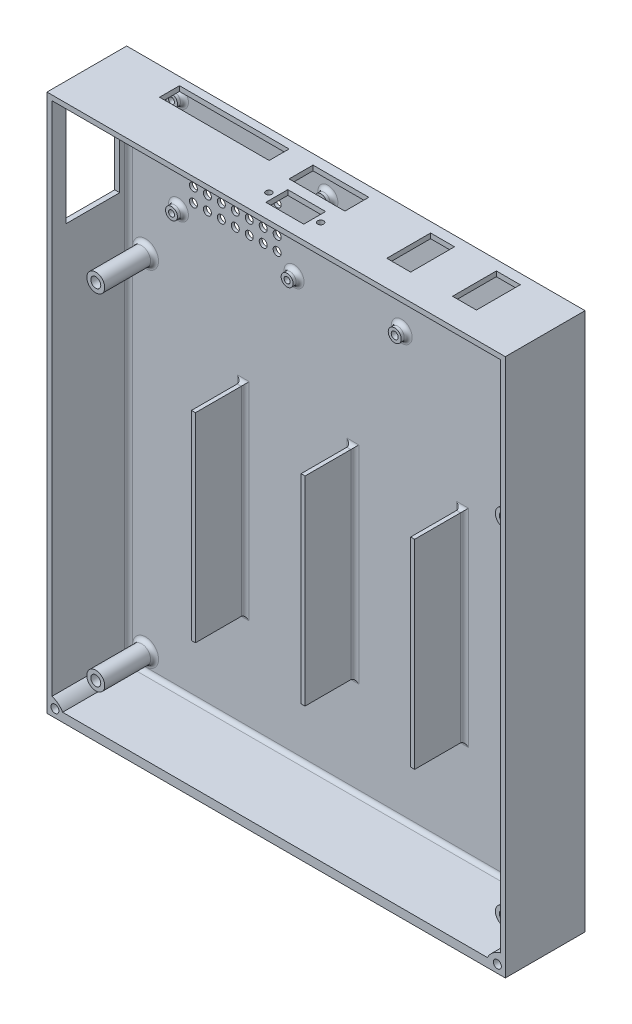
SolidWorks part; units mm, degrees
ref_plane "Plan de face" through (0, 0, 0) normal (0, 0, 1) x (1, 0, 0)
ref_plane "Plan de dessus" through (0, 0, 0) normal (0, 1, 0) x (1, 0, 0)
ref_plane "Plan de droite" through (0, 0, 0) normal (1, 0, 0) x (0, 0, -1)
sketch "Esquisse1" plane through (0, 0, 0) normal (0, 0, 1) x (1, 0, 0)
  line L0 (0, 136.5625) -> (0, -142.8125) construction
  line L1 (-195, -41.5625) -> (201.25, -41.5625) construction
  line L2 (115, 93.4375) -> (-115, 93.4375)
  line L3 (-115, 93.4375) -> (-115, -176.5625)
  line L4 (115, -176.5625) -> (-115, -176.5625)
  line L6 (115, 93.4375) -> (115, -176.5625)
  point P10 (-115, -41.5625)
  point P12 (0, 93.4375)
  dimension "D1" = 115
  dimension "D2" = 135
extrude "Boss.-Extru.1" add sketch "Esquisse1" along normal blind 5
sketch "Esquisse2" plane through (0, 0, 5) normal (0, 0, 1) x (1, 0, 0)
  line L0 (-115, -176.5625) -> (115, -176.5625) construction
  line L1 (-115, 93.4375) -> (-115, -176.5625) construction
  line L2 (-1.5, 152.9836) -> (-1.5, -221.0762) construction
  line L3 (-154.951, -77.0625) -> (207.3243, -77.0625) construction
  line L4 (115, 93.4375) -> (-115, 93.4375) construction
  line L5 (115, -176.5625) -> (115, 93.4375) construction
  line L6 (152.1134, 61.4375) -> (-165.3137, 61.4375) construction
  line L7 (-58.5, 134.3556) -> (-58.5, 23.9251) construction
  line L8 (-25.2083, 61.4375) -> (-76.5448, 61.4375) construction
  line L9 (-2, 113.0864) -> (-2, 66.437) construction
  line L10 (-19.2346, 73.6875) -> (13.2189, 73.6875) construction
  circle A0 centre (-104, -163.5625) radius 2
  circle A7 centre (-104, 9.4375) radius 2
  circle A8 centre (104.5, 82.9375) radius 1.75
  circle A9 centre (24.5, 82.9375) radius 1.75
  circle A10 centre (24.5, 39.9375) radius 1.75
  circle A11 centre (104.5, 39.9375) radius 1.75
  circle A12 centre (-87.5, 85.9375) radius 1.5
  circle A13 centre (-29.5, 85.9375) radius 1.5
  circle A116 centre (8.5, 67.4375) radius 1.5
  circle A117 centre (-12.5, 67.4375) radius 1.5
  circle A118 centre (-12.5, 79.9375) radius 1.5
  circle A119 centre (8.5, 79.9375) radius 1.5
  circle A120 centre (101, -163.5625) radius 2
  circle A121 centre (101, 9.4375) radius 2
  circle A122 centre (-87.5, 36.9375) radius 1.5
  circle A123 centre (-29.5, 36.9375) radius 1.5
  dimension "D1" = 4
  dimension "D4" = 26
  dimension "D10" = 3.5
  dimension "D11" = 3.5
  dimension "D13" = 3
  dimension "D17" = 24.5
  dimension "D21" = 10.5
  dimension "D22" = 3
  dimension "D20" = 102.5
  dimension "D2" = 13
  dimension "D3" = 11
  dimension "D5" = 86.5
  dimension "D6" = 10.5
  dimension "D7" = 10.5
  dimension "D8" = 10.5
  dimension "D9" = 80
  dimension "D12" = 21.5
  dimension "D14" = 27.5
  dimension "D15" = 7.5
  dimension "D16" = 29
  dimension "D23" = 6.25
extrude "Enlèv. mat.-Extru.1" cut sketch "Esquisse2" against normal blind 5
shell "Coque3" thickness 1.5 removed face at (102.75, 39.9375, 5)
sketch "Esquisse3" plane through (0, 0, 1.5) normal (0, 0, 1) x (1, 0, 0)
  line L0 (-1.5, 104.4372) -> (-1.5, -196.0583) construction
  line L1 (104, -77.0625) -> (-172.0752, -77.0625) construction
  circle A0 centre (-104, 9.4375) radius 4.5
  circle A4 centre (-104, -163.5625) radius 4.5
  circle A5 centre (-104, 9.4375) radius 2.5
  circle A6 centre (-104, -163.5625) radius 2.5
  circle A8 centre (101, -163.5625) radius 4.5
  circle A9 centre (101, -163.5625) radius 2.5
  circle A10 centre (101, 9.4375) radius 4.5
  circle A11 centre (101, 9.4375) radius 2.5
  circle A12 centre (-104, -163.5625) radius 3.5 construction
  dimension "D1" = 9
  dimension "D2" = 5
  dimension "D4" = 102.5
  dimension "D3" = 86.5
extrude "Boss.-Extru.3" add sketch "Esquisse3" along normal blind 25
sketch "Esquisse4" plane through (0, 0, 1.5) normal (0, 0, 1) x (1, 0, 0)
  line L0 (-113.5, -175.0625) -> (113.5, -175.0625) construction
  line L1 (-113.5, 91.9375) -> (-112.5, 91.9375)
  line L2 (-113.5, 91.9375) -> (-113.5, -175.0625)
  line L3 (-113.5, -175.0625) -> (-112.5, -175.0625)
  line L4 (-112.5, 91.9375) -> (-112.5, -175.0625)
  line L5 (0, 95.4885) -> (0, -188.2553) construction
  line L6 (113.5, -175.0625) -> (112.5, -175.0625)
  line L7 (113.5, 91.9375) -> (113.5, -175.0625)
  line L8 (113.5, 91.9375) -> (112.5, 91.9375)
  line L9 (112.5, 91.9375) -> (112.5, -175.0625)
  dimension "D1" = 1
extrude "Boss.-Extru.4" add sketch "Esquisse4" along normal blind 3.5
sketch "Esquisse5" plane through (0, 0, 1.5) normal (0, 0, 1) x (1, 0, 0)
  line L0 (112.5, 91.9375) -> (112.5, -175.0625) construction
  line L1 (-112.5, 91.9375) -> (112.5, 91.9375)
  line L2 (-112.5, 91.9375) -> (-112.5, 90.9375)
  line L3 (-112.5, 90.9375) -> (112.5, 90.9375)
  line L4 (112.5, 91.9375) -> (112.5, 90.9375)
  line L5 (-112.5, -175.0625) -> (-112.5, 91.9375) construction
  line L6 (-196.2712, -42.5625) -> (155.2477, -42.5625) construction
  line L7 (-112.5, -172.1625) -> (112.5, -172.1625)
  line L8 (-112.5, -172.1625) -> (-112.5, -175.0625)
  line L9 (-112.5, -175.0625) -> (112.5, -175.0625)
  line L10 (112.5, -172.1625) -> (112.5, -175.0625)
  dimension "D1" = 1
  dimension "D2" = 133.5
  dimension "D3" = 2.9
extrude "Boss.-Extru.10" add sketch "Esquisse5" along normal blind 3.5
sketch "Esquisse7" plane through (0, 0, 1.5) normal (0, 0, 1) x (1, 0, 0)
  line L0 (1, -22.1625) -> (1, -122.1625)
  line L5 (-1, -22.1625) -> (1, -22.1625)
  line L6 (-151.213, -61.5625) -> (245.9243, -61.5625) construction
  line L57 (-1, -22.1625) -> (-1, -122.1625)
  line L58 (-56, -22.1625) -> (-54, -22.1625)
  line L59 (-56, -22.1625) -> (-56, -122.1625)
  line L60 (-56, -122.1625) -> (-54, -122.1625)
  line L61 (-54, -22.1625) -> (-54, -122.1625)
  line L62 (-1, -122.1625) -> (1, -122.1625)
  line L63 (56, -22.1625) -> (56, -122.1625)
  line L64 (54, -22.1625) -> (56, -22.1625)
  line L65 (54, -22.1625) -> (54, -122.1625)
  line L66 (54, -122.1625) -> (56, -122.1625)
  line L67 (-112.5, -172.1625) -> (-112.5, 90.9375) construction
  line L68 (112.5, -172.1625) -> (-112.5, -172.1625) construction
  dimension "D1" = 2
  dimension "D2" = 100
  dimension "D3" = 3
  dimension "D4" = 56.5
  dimension "D5" = 50
extrude "Boss.-Extru.11" add sketch "Esquisse7" along normal blind 25
sketch "Esquisse8" plane through (0, 0, 5) normal (0, 0, 1) x (1, 0, 0)
  line L0 (-112.5, 90.9375) -> (-112.5, -172.1625)
  line L1 (-112.5, -172.1625) -> (112.5, -172.1625)
  line L2 (112.5, -172.1625) -> (112.5, 90.9375)
  line L3 (112.5, 90.9375) -> (-112.5, 90.9375)
  line L4 (-115, 93.4375) -> (-115, -176.5625)
  line L5 (-115, -176.5625) -> (115, -176.5625)
  line L6 (115, -176.5625) -> (115, 93.4375)
  line L7 (115, 93.4375) -> (-115, 93.4375)
extrude "Boss.-Extru.12" add sketch "Esquisse8" along normal blind 35
fillet "Congé1" radius 2 32 edges at (-54, -72.1625, 1.5) (-55, -22.1625, 1.5) (-56, -72.1625, 1.5) (-108.5, -163.5625, 1.5) (96.5, -163.5625, 1.5) (-108.5, 9.4375, 1.5) (-90.5, 85.9375, 1.5) (-32.5, 85.9375, 1.5) (5.5, 67.4375, 1.5) (101.25, 82.9375, 1.5) (21.25, 82.9375, 1.5) (21.25, 39.9375, 1.5) (101.25, 39.9375, 1.5) (5.5, 79.9375, 1.5) (-15.5, 79.9375, 1.5) (-15.5, 67.4375, 1.5) (-112.5, -40.6125, 1.5) (0, 90.9375, 1.5) (112.5, -40.6125, 1.5) (0, -172.1625, 1.5) (96.5, 9.4375, 1.5) (-90.5, 36.9375, 1.5) (-32.5, 36.9375, 1.5) (55, -122.1625, 1.5) (56, -72.1625, 1.5) (55, -22.1625, 1.5) (54, -72.1625, 1.5) (-55, -122.1625, 1.5) (0, -122.1625, 1.5) (1, -72.1625, 1.5) (0, -22.1625, 1.5) (-1, -72.1625, 1.5)
sketch "Esquisse11" plane through (0, 90.9375, 0) normal (0, -1, 0) x (1, 0, 0)
  line L0 (-112.5, 3.5) -> (112.5, 3.5) construction
  line L1 (-84.5, 14) -> (-29.5, 14)
  line L2 (-84.5, 14) -> (-84.5, 4)
  line L3 (-84.5, 4) -> (-29.5, 4)
  line L4 (-29.5, 14) -> (-29.5, 4)
  line L5 (-112.5, 40) -> (-112.5, 3.5) construction
  line L6 (112.5, 40) -> (-112.5, 40) construction
  line L7 (-16.5, 17) -> (11.5, 17)
  line L8 (-16.5, 17) -> (-16.5, 5)
  line L9 (-16.5, 5) -> (11.5, 5)
  line L10 (11.5, 17) -> (11.5, 5)
  line L11 (42.5, 27) -> (54.5, 27)
  line L12 (42.5, 27) -> (42.5, 5)
  line L13 (42.5, 5) -> (54.5, 5)
  line L14 (54.5, 27) -> (54.5, 5)
  line L16 (115, 0) -> (-115, 0) construction
  line L17 (76.86, 6.6) -> (86.86, 6.6) construction
  line L18 (75.5, 27) -> (87.5, 27)
  line L19 (75.5, 27) -> (75.5, 5)
  line L20 (75.5, 5) -> (87.5, 5)
  line L21 (87.5, 27) -> (87.5, 5)
  dimension "D2" = 10
  dimension "D3" = 55
  dimension "D4" = 28
  dimension "D5" = 12
  dimension "D6" = 28
  dimension "D7" = 13
  dimension "D8" = 12
  dimension "D9" = 31
  dimension "D10" = 13
  dimension "D11" = 1.5
  dimension "D12" = 4
  dimension "D13" = 21
  dimension "D14" = 12
  dimension "D15" = 13
  dimension "D16" = 1.6
extrude "Enlèv. mat.-Extru.3" cut sketch "Esquisse11" against normal blind 10
sketch "Esquisse13" plane through (-112.5, 0, 0) normal (1, 0, 0) x (0, 0, -1)
  line L2 (-33, 88.9375) -> (-33, 33.9375)
  line L6 (-40, 93.4375) -> (-40, -176.5625) construction
  line L8 (-33, 88.9375) -> (-6, 88.9375)
  line L9 (-6, 88.9375) -> (-6, 33.9375)
  line L10 (-6, 33.9375) -> (-33, 33.9375)
  line L11 (-40, 93.4375) -> (0, 93.4375) construction
  line L12 (0, 93.4375) -> (0, -176.5625) construction
  dimension "D1" = 4.5
  dimension "D2" = 55
  dimension "D3" = 7
  dimension "D4" = 6
extrude "Enlèv. mat.-Extru.4" cut sketch "Esquisse13" against normal blind 10
sketch "Esquisse14" plane through (0, 0, 1.5) normal (0, 0, 1) x (1, 0, 0)
  line L0 (-33.5, 88.9375) -> (-83.5, 88.9375) construction
  line L1 (-110.5, 88.9375) -> (-110.5, 9.4375) construction
  circle A0 centre (-80, 78.4375) radius 2
  circle A1 centre (-73, 78.4375) radius 2
  circle A2 centre (-66, 78.4375) radius 2
  circle A3 centre (-59, 78.4375) radius 2
  circle A4 centre (-52, 78.4375) radius 2
  circle A5 centre (-45, 78.4375) radius 2
  circle A6 centre (-38, 78.4375) radius 2
  circle A7 centre (-73, 71.4375) radius 2
  circle A8 centre (-66, 71.4375) radius 2
  circle A9 centre (-59, 71.4375) radius 2
  circle A10 centre (-52, 71.4375) radius 2
  circle A11 centre (-45, 71.4375) radius 2
  circle A12 centre (-38, 71.4375) radius 2
  circle A13 centre (-73, 64.4375) radius 2
  circle A14 centre (-66, 64.4375) radius 2
  circle A15 centre (-59, 64.4375) radius 2
  circle A16 centre (-52, 64.4375) radius 2
  circle A17 centre (-45, 64.4375) radius 2
  circle A18 centre (-38, 64.4375) radius 2
  circle A19 centre (-73, 57.4375) radius 2
  circle A20 centre (-66, 57.4375) radius 2
  circle A21 centre (-59, 57.4375) radius 2
  circle A22 centre (-52, 57.4375) radius 2
  circle A23 centre (-45, 57.4375) radius 2
  circle A24 centre (-38, 57.4375) radius 2
  circle A25 centre (-73, 50.4375) radius 2
  circle A26 centre (-66, 50.4375) radius 2
  circle A27 centre (-59, 50.4375) radius 2
  circle A28 centre (-52, 50.4375) radius 2
  circle A29 centre (-45, 50.4375) radius 2
  circle A30 centre (-38, 50.4375) radius 2
  circle A31 centre (-73, 43.4375) radius 2
  circle A32 centre (-66, 43.4375) radius 2
  circle A33 centre (-59, 43.4375) radius 2
  circle A34 centre (-52, 43.4375) radius 2
  circle A35 centre (-45, 43.4375) radius 2
  circle A36 centre (-38, 43.4375) radius 2
  circle A37 centre (-80, 71.4375) radius 2
  circle A38 centre (-80, 64.4375) radius 2
  circle A39 centre (-80, 57.4375) radius 2
  circle A40 centre (-80, 50.4375) radius 2
  circle A41 centre (-80, 43.4375) radius 2
  dimension "D1" = 4
  dimension "D2" = 10.5
  dimension "D3" = 30.5
  dimension "D4" = 7
  dimension "D5" = 6
extrude "Enlèv. mat.-Extru.5" cut sketch "Esquisse14" against normal blind 10
sketch "Esquisse15" plane through (0, 0, 0) normal (0, 0, -1) x (-1, 0, 0)
  line L0 (115, -176.5625) -> (-115, -176.5625) construction
  line L1 (115, -176.5625) -> (106, -176.5625)
  line L2 (115, -176.5625) -> (115, -167.5625)
  line L5 (115, 93.4375) -> (115, -176.5625) construction
  arc A0 (115, -167.5625) -> (106, -176.5625) centre (115, -176.5625) ccw
  dimension "D1" = 0
  dimension "D2" = 0
extrude "Boss.-Extru.13" add sketch "Esquisse15" against normal up to surface (40 mm away) up to face at (0, -41.5625, 40)
sketch "Esquisse16" plane through (0, 0, 26.5) normal (0, 0, 1) x (1, 0, 0)
  line L0 (115, -176.5625) -> (115, 93.4375) construction
  line L3 (105, -176.5625) -> (115, -176.5625)
  line L4 (115, -166.5625) -> (115, -176.5625)
  line L5 (-115, -176.5625) -> (115, -176.5625) construction
  arc A1 (105, -176.5625) -> (115, -166.5625) centre (115, -176.5625) cw
  dimension "D1" = 0
  dimension "D2" = 0
extrude "Boss.-Extru.14" add sketch "Esquisse16" against normal up to surface (26.5 mm away) from surface up to face at (0, -41.5625, 0) starting at face at (-21.3461, -65.9679, 40)
sketch "Esquisse17" plane through (0, 0, 26.5) normal (0, 0, 1) x (1, 0, 0)
  line L0 (-115, -176.5625) -> (115, -176.5625) construction
  line L2 (-115, 93.4375) -> (-115, -176.5625) construction
  circle A0 centre (-111, -172.5625) radius 2
  dimension "D1" = 4
  dimension "D2" = 4
extrude "Enlèv. mat.-Extru.6" cut sketch "Esquisse17" against normal up to surface (26.5 mm away) from surface up to face at (0, -41.5625, 0) starting at face at (-0.2148, -82.6683, 40)
sketch "Esquisse18" plane through (0, 0, 26.5) normal (0, 0, 1) x (1, 0, 0)
  line L0 (-115, -176.5625) -> (115, -176.5625) construction
  line L1 (115, -176.5625) -> (115, 93.4375) construction
  circle A0 centre (111, -172.5625) radius 2
  dimension "D1" = 4
  dimension "D2" = 4
extrude "Enlèv. mat.-Extru.7" cut sketch "Esquisse18" against normal up to surface (26.5 mm away) from surface up to face at (-113, -172.5625, 0) starting at face at (-109, -172.5625, 40)
sketch "Esquisse21" plane through (0, 93.4375, 0) normal (0, 1, 0) x (1, 0, 0)
  line L0 (115, -40) -> (-115, -40) construction
  line L1 (-12.1571, -22) -> (6.8429, -22)
  line L2 (-12.1571, -22) -> (-12.1571, -33)
  line L3 (-12.1571, -33) -> (6.8429, -33)
  line L4 (6.8429, -22) -> (6.8429, -33)
  circle A0 centre (10.3429, -28) radius 1.5
  circle A1 centre (-15.6571, -28) radius 1.5
  point P8 (6.8429, -27.5)
  point P13 (-16.2452, -27.6828)
  dimension "D2" = 3.5
  dimension "D3" = 26
  dimension "D4" = 5
  dimension "D1" = 7
  dimension "D5" = 5
  dimension "D6" = 19
extrude "Enlèv. mat.-Extru.8" cut sketch "Esquisse21" against normal up to surface (2.5 mm away) up to face at (-57, 90.9375, 9)
